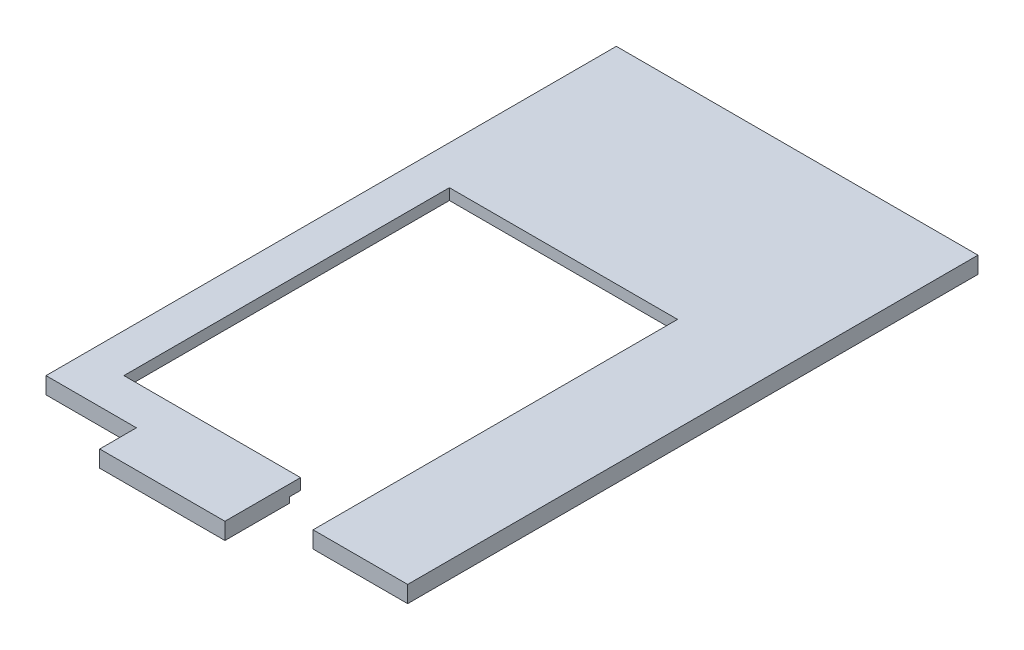
SolidWorks part; units mm, degrees
ref_plane "Front Plane" through (0, 0, 0) normal (0, 0, 1) x (1, 0, 0)
ref_plane "Top Plane" through (0, 0, 0) normal (0, 1, 0) x (1, 0, 0)
ref_plane "Right Plane" through (0, 0, 0) normal (1, 0, 0) x (0, 0, -1)
sketch "Sketch1" plane through (0, 55.3432, 0) normal (0, 1, 0) x (1, 0, 0)
  line L8 (-104.6818, -229.0452) -> (-59.6818, -229.0452)
  line L9 (-59.6818, -229.0452) -> (-59.6818, -215.8616)
  line L10 (-59.6818, -215.8616) -> (-7.1818, -215.8616)
  line L11 (-7.1818, -215.8616) -> (-7.1818, -10.8616)
  line L12 (-7.1818, -10.8616) -> (-137.1818, -10.8616)
  line L13 (-137.1818, -10.8616) -> (-137.1818, -215.8616)
  line L14 (-137.1818, -215.8616) -> (-104.6818, -215.8616)
  line L15 (-104.6818, -215.8616) -> (-104.6818, -229.0452)
  line L16 (-104.6818, -229.0452) -> (-59.6818, -229.0452)
  line L17 (-59.6818, -229.0452) -> (-59.6818, -215.8616)
  line L18 (-59.6818, -215.8616) -> (-7.1818, -215.8616)
  line L19 (-7.1818, -215.8616) -> (-7.1818, -10.8616)
  line L20 (-7.1818, -10.8616) -> (-137.1818, -10.8616)
  line L21 (-137.1818, -10.8616) -> (-137.1818, -215.8616)
  line L22 (-137.1818, -215.8616) -> (-104.6818, -215.8616)
  line L23 (-104.6818, -215.8616) -> (-104.6818, -229.0452)
  line L33 (-7.1818, -215.8616) -> (-7.1818, -10.8616) construction
  point P6 (0, 0)
  point P8 (0, 0)
  line M9 (-104.6818, -229.0452) -> (-59.6818, -229.0452)
  line M10 (-59.6818, -229.0452) -> (-59.6818, -215.8616)
  line M11 (-59.6818, -215.8616) -> (-7.1818, -215.8616)
  line M12 (-7.1818, -215.8616) -> (-7.1818, -10.8616)
  line M13 (-7.1818, -10.8616) -> (-137.1818, -10.8616)
  line M14 (-137.1818, -10.8616) -> (-137.1818, -215.8616)
  line M15 (-137.1818, -215.8616) -> (-104.6818, -215.8616)
  line M16 (-104.6818, -215.8616) -> (-104.6818, -229.0452)
  line M17 (-37.1818, -80.8616) -> (-37.1818, -205.8616)
  line M18 (-37.1818, -205.8616) -> (-127.1818, -205.8616)
  line M19 (-127.1818, -205.8616) -> (-127.1818, -80.8616)
  line M20 (-127.1818, -80.8616) -> (-37.1818, -80.8616)
  dimension "D1" = 0
extrude "Boss-Extrude1" add sketch "Sketch1" along normal blind 6 contours M16 M9 M10 M11 M12 M13 M14 M15 M20 M17 M18 M19 region at (-102.1421, 55.3432, 222.4534)
sketch "Sketch2" plane through (0, 61.3432, 0) normal (0, 1, 0) x (1, 0, 0)
  line L0 (-127.1818, -80.8616) -> (-37.1818, -80.8616) construction
  line L1 (-127.1818, -205.8616) -> (-127.1818, -80.8616) construction
  line L2 (-37.1818, -205.8616) -> (-127.1818, -205.8616) construction
  line L3 (-37.1818, -80.8616) -> (-37.1818, -205.8616) construction
  line L4 (-127.1818, -80.8616) -> (-37.1818, -80.8616)
  line L5 (-127.1818, -205.8616) -> (-127.1818, -80.8616)
  line L6 (-37.1818, -205.8616) -> (-127.1818, -205.8616)
  line L7 (-37.1818, -80.8616) -> (-37.1818, -205.8616)
  line L8 (-123.1818, -201.8616) -> (-123.1818, -84.8616)
  line L9 (-123.1818, -84.8616) -> (-41.1818, -84.8616)
  line L10 (-41.1818, -84.8616) -> (-41.1818, -201.8616)
  line L11 (-41.1818, -201.8616) -> (-123.1818, -201.8616)
  dimension "D1" = 4
extrude "Boss-Extrude2" add sketch "Sketch2" against normal up to surface (4 mm away)
sketch "Sketch3" plane through (0, 61.3432, 0) normal (0, 1, 0) x (1, 0, 0)
  line L0 (-59.6818, -234.0452) -> (-59.6818, -150.3652) construction
  line L1 (-59.6818, -201.8616) -> (-41.1818, -201.8616)
  line L2 (-59.6818, -201.8616) -> (-59.6818, -215.8616)
  line L3 (-59.6818, -215.8616) -> (-41.1818, -215.8616)
  line L4 (-41.1818, -201.8616) -> (-41.1818, -215.8616)
  line L5 (-123.1818, -201.8616) -> (-41.1818, -201.8616) construction
  line L6 (-59.6818, -215.8616) -> (-7.1818, -215.8616) construction
  line L7 (-41.1818, -201.8616) -> (-41.1818, -84.8616) construction
extrude "Cut-Extrude1" cut sketch "Sketch3" against normal blind 10 contours L2 L1 L4 L3
